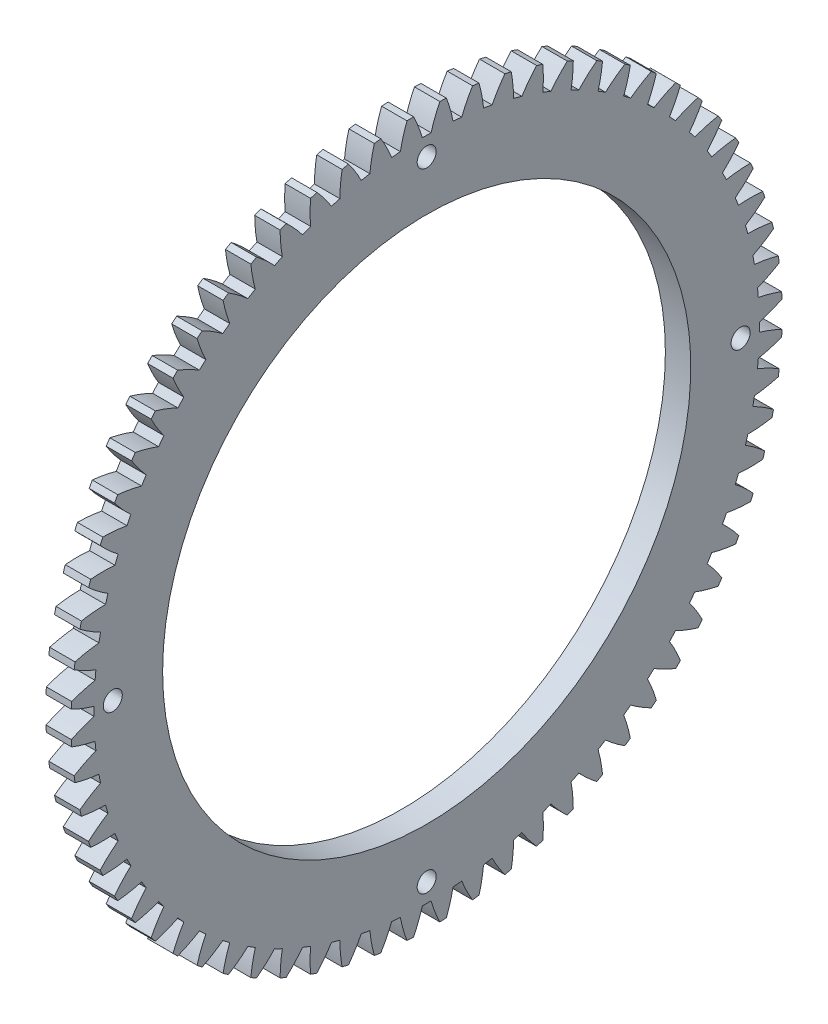
SolidWorks part; units mm, degrees
ref_plane "Plane1" through (0, 0, 0) normal (0, 0, 1) x (1, 0, 0)
ref_plane "Plane2" through (0, 0, 0) normal (0, 1, 0) x (1, 0, 0)
ref_plane "Plane3" through (0, 0, 0) normal (1, 0, 0) x (0, 0, -1)
sketch "HoldingSke" plane through (0, 0, 0) normal (0, 1, 0) x (1, 0, 0)
  line L0 (0, 0) -> (95.1501, -235.5047)
  line L1 (-15, 0) -> (100, 0) construction
  line L2 (0, 0) -> (-2.1039, 2.3779)
  line L3 (0, 0) -> (-11.863, 4.5341)
  line L4 (0, 0) -> (3.2351, 8.0072)
  line L5 (0, 0) -> (-47.5972, -17.7524)
  line L6 (0, 0) -> (-5.2639, -3.5516)
  line L7 (-2.1039, 2.3779) -> (8.8308, 51.9871)
  line L8 (-76.2, 54.61) -> (92.964, 54.61)
  line L9 (-71.009, 38.7566) -> (-53.1078, 45.2721)
  line L10 (-76.2, 71.12) -> (104.1128, 71.12)
  line L11 (0, 0) -> (-6.35, 0)
  line L12 (-76.2, 101.6) -> (-76.0984, 101.6)
  line L13 (24.9733, 27.94) -> (52.9518, 28.4284)
  line L14 (24.9733, 27.94) -> (24.9746, 27.94)
  line L15 (24.9733, 27.94) -> (100.4006, 29.5858)
  circle A0 centre (0, 0) radius 76.2
  circle A1 centre (0, 0) radius 38.1
  circle A2 centre (0, 0) radius 38.1
  circle A3 centre (0, 0) radius 76.2
  dimension "Num_teeth" = 68
  dimension "H" = 19.05
  dimension "Pitch_radius" = 180.3128
  dimension "Width" = 6.35
  dimension "Thickness" = 6.35
sketch "BasProSke" plane through (0, 0, 0) normal (0, 1, 0) x (1, 0, 0)
  line L0 (-10, 0) -> (60, 0) construction
  line L1 (0, 0) -> (0, 88.9)
  line L2 (0, 0) -> (6.35, 0)
  line L3 (6.35, 0) -> (6.35, 88.9)
  line L4 (6.35, 88.9) -> (0, 88.9)
  dimension "Thickness" = 6.35
  dimension "Diameter" = 177.8
revolve "Base-Revolve" add sketch "BasProSke" angle 360 about L0
sketch "TooCutSke" plane through (0, 0, 0) normal (1, 0, 0) x (0, 0, -1)
  line L1 (0, 0) -> (0, 107) construction
  line L2 (0, 0) -> (-2.1725, 86.3327) construction
  line L3 (0, 0) -> (-7.975, 172.4975) construction
  line L4 (-2.1725, 86.3327) -> (-3.9875, 86.2488) construction
  arc A0 (1.0901, 83.1766) -> (-1.0901, 83.1766) centre (0, 0) ccw
  arc A1 (3.2994, 88.8642) -> (-3.2994, 88.8642) centre (0, 0) ccw
  circle A2 centre (0, 0) radius 86.36 construction
  circle A3 centre (0, 0) radius 81.1519 construction
  arc A4 (-1.0901, 83.1766) -> (-3.2994, 88.8642) centre (-34.2689, 73.5613) ccw
  arc A5 (3.2994, 88.8642) -> (1.0901, 83.1766) centre (34.2689, 73.5613) ccw
extrude "ToothCut" cut sketch "TooCutSke" along normal through all
fillet "Breaks" [suppressed] radius 0.0508 tangent propagation no
fillet "RootFillets" [suppressed] radius 0.6363
pattern_circular "TeethCuts" count 68 every 5.294 about axis through (-10, 0, 0) along (1, 0, 0) of "ToothCut", "RootFillets", "Breaks"
sketch "HubNeaOneSke" plane through (0, 0, 0) normal (-1, 0, 0) x (0, 0, 1)
  circle A0 centre (0, 0) radius 38.1
  dimension "Diameter" = 76.2
extrude "HubNearOne" [suppressed] add sketch "HubNeaOneSke" along normal blind 44.4501
sketch "HubNeaBotSke" plane through (0, 0, 0) normal (-1, 0, 0) x (0, 0, 1)
  circle A0 centre (0, 0) radius 38.1
  dimension "Diameter" = 76.2
extrude "HubNearBoth" [suppressed] add sketch "HubNeaBotSke" along normal blind 22.225
ref_plane "FarPln" through (6.35, 0, 0) normal (1, 0, 0) x (0, 0, -1)
sketch "HubFarSke" plane through (6.35, 0, 0) normal (1, 0, 0) x (0, 0, -1)
  circle A0 centre (0, 0) radius 38.1
  dimension "Diameter" = 76.2
extrude "HubFar" [suppressed] add sketch "HubFarSke" along normal blind 22.225
sketch "BorSke" plane through (0, 0, 0) normal (1, 0, 0) x (0, 0, -1)
  circle A0 centre (0, 0) radius 66.04
  dimension "D1" = 132.08
extrude "Bore" cut sketch "BorSke" along normal mid plane 101.6001
sketch "KeySke" plane through (0, 0, 0) normal (1, 0, 0) x (0, 0, -1)
  line L0 (-19.05, 0) -> (-19.05, 92.964)
  line L1 (-19.05, 92.964) -> (19.05, 92.964)
  line L2 (19.05, 92.964) -> (19.05, 0)
  line L3 (0, 0) -> (0, 34) construction
  line L4 (-19.05, 0) -> (19.05, 0)
  dimension "Width" = 38.1
extrude "Keyway" [suppressed] cut sketch "KeySke" along normal mid plane 101.6001
pattern_circular "Keyway2" [suppressed] count 2 every 90 about axis through (-10, 0, 0) along (1, 0, 0) reverse direction yes
sketch "Sketch2" plane through (6.35, 0, 0) normal (1, 0, 0) x (0, 0, -1)
  line L0 (0, 78.5) -> (0, 0) construction
  line L7 (78.5, 0) -> (0, 0) construction
  circle A0 centre (0, 0) radius 85.5 construction
  circle A1 centre (0, 78.5) radius 2.3812
  circle A2 centre (78.5, 0) radius 2.3813
  circle A3 centre (0, -78.5) radius 2.3813
  circle A4 centre (-78.5, 0) radius 2.3813
  point P3 (6.9506, -0.2673)
  point P4 (0, 0)
  point P5 (0, 0)
  point P18 (0, 0)
  dimension "D1" = 171
  dimension "D4" = 4.7625
  dimension "D5" = 78.5
  dimension "D6" = 4
extrude "Cut-Extrude1" cut sketch "Sketch2" against normal through all contours A4 | A3 | A2 | A1
equation "' \"Pitch@HoldingSke\" = 4"
equation "' \"Num_teeth@HoldingSke\" = 12"
equation "' \"Ap@HoldingSke\" =  20"
equation "' \"Ap@HoldingSke\" = 20"
equation "' \"Width@HoldingSke\" = 0.5"
equation "' \"Hub_dia@HoldingSke\"= 1"
equation "' \"Hub_dia@HoldingSke\" = 1"
equation "' \"Overall_len@HoldingSke\" = 1.0"
equation "' \"Bore@HoldingSke\" = 0.75"
equation "' \"T_dim@HoldingSke\" = 0.85"
equation "' \"Width@KeySke\" = 0.25"
equation "' \"Show_teeth@HoldingSke\" = 13"
equation "' \"Backlash@HoldingSke\" = 0.009"
equation "' \"Addendum_fac@HoldingSke\" = 1.0"
equation "' \"Dedendum_fac@HoldingSke\" = 1.25"
equation "' \"Dedendum_add@HoldingSke\" = 0.00005"
equation "' \"Clearance_fac@HoldingSke\" = 0.25"
equation "' \"Pitch@HoldingSke\" = 0.5"
equation "' \"Num_teeth@HoldingSke\" = 23"
equation "' \"Show_teeth@HoldingSke\" = 23"
equation "' \"Backlash@HoldingSke\" = 0.0375"
equation "\"Overcut_dia@TooCutSke\" = (\"Num_teeth@HoldingSke\" + 2 * \"Addendum_fac@HoldingSke\") / \"Pitch@HoldingSke\" + 0.002"
equation "\"Pitch_dia@TooCutSke\" = \"Num_teeth@HoldingSke\" / \"Pitch@HoldingSke\""
equation "\"Base_dia@TooCutSke\" = \"Num_teeth@HoldingSke\" / \"Pitch@HoldingSke\" * cos((\"Ap@HoldingSke\"  * 3.14159265 / 180))"
equation "\"Root_dia@TooCutSke\" = (\"Num_teeth@HoldingSke\" + 2) / \"Pitch@HoldingSke\" - 2 * (\"Addendum_fac@HoldingSke\" + \"Dedendum_fac@HoldingSke\") / \"Pitch@HoldingSke\" - \"Dedendum_add@HoldingSke\" * 2"
equation "\"Half_ang@TooCutSke\" = 180 / \"Num_teeth@HoldingSke\""
equation "\"Half_CT@TooCutSke\" = \"Num_teeth@HoldingSke\" / \"Pitch@HoldingSke\" * sin((3.14159265 / 2 / \"Num_teeth@HoldingSke\")) / 2 - 7 * \"Backlash@HoldingSke\" / 4"
equation "\"Flank_rad@TooCutSke\" = \"Num_teeth@HoldingSke\" / \"Pitch@HoldingSke\" / 5"
equation "\"Radius@RootFillets\" = \"Clearance_fac@HoldingSke\" / \"Pitch@HoldingSke\" + \"Dedendum_add@HoldingSke\""
equation "\"Break_rad@Breaks\" = 0.02 / \"Pitch@HoldingSke\""
equation "\"Thickness@HoldingSke\" = \"Width@HoldingSke\""
equation "\"OAL@HoldingSke\" = \"Thickness@HoldingSke\""
equation "\"MHD@HoldingSke\" = (\"Num_teeth@HoldingSke\" + 2) / \"Pitch@HoldingSke\" - 2 * (\"Addendum_fac@HoldingSke\" + \"Dedendum_fac@HoldingSke\")  / \"Pitch@HoldingSke\" - \"Dedendum_add@HoldingSke\" * 2"
equation "\"MBD@HoldingSke\" = (\"Num_teeth@HoldingSke\" + 2) / \"Pitch@HoldingSke\" - 2 * (\"Addendum_fac@HoldingSke\" + \"Dedendum_fac@HoldingSke\")  / \"Pitch@HoldingSke\" - \"Dedendum_add@HoldingSke\" * 2 - 0.002"
equation "\"MHD@HoldingSke\" = ((sgn( \"MHD@HoldingSke\" - \"Hub_dia@HoldingSke\" )-1)*( \"MHD@HoldingSke\" - \"Hub_dia@HoldingSke\" ))/-2+ \"Hub_dia@HoldingSke\""
equation "\"MBD@HoldingSke\" = ((sgn( \"MBD@HoldingSke\" - \"Bore@HoldingSke\" )-1)*( \"MBD@HoldingSke\" - \"Bore@HoldingSke\" ))/-2+ \"Bore@HoldingSke\""
equation "\"OAL@HoldingSke\" = ((sgn( \"OAL@HoldingSke\" - \"Overall_len@HoldingSke\" )+1)*( \"OAL@HoldingSke\" - \"Overall_len@HoldingSke\" ))/2 + \"Overall_len@HoldingSke\" + 0.000002"
equation "\"Num_teeth@TeethCuts\" = int( \"Show_teeth@HoldingSke\" ) + 1"
equation "\"Num_teeth@TeethCuts\" = ((sgn( \"Num_teeth@TeethCuts\" - \"Num_teeth@HoldingSke\" )-1)*( \"Num_teeth@TeethCuts\" - \"Num_teeth@HoldingSke\" ))/-2+ \"Num_teeth@HoldingSke\""
equation "\"Num_teeth@TeethCuts\" = ((sgn( \"Num_teeth@TeethCuts\" - 2.0)+1)*( \"Num_teeth@TeethCuts\" - 2.0))/2 +2.0"
equation "\"Angle@TeethCuts\" = 360.0 / \"Num_teeth@HoldingSke\""
equation "\"Diameter@BasProSke\" = (\"Num_teeth@HoldingSke\" + 2 * \"Addendum_fac@HoldingSke\") / \"Pitch@HoldingSke\""
equation "\"Thickness@BasProSke\"  = \"Thickness@HoldingSke\""
equation "' \"Fillet_rad@BasProSke\" =  \"Thickness@HoldingSke\" * 0.05"
equation "' \"Fillet_rad@BasProSke\" = \"Thickness@HoldingSke\" * 0.05"
equation "\"MHD@HoldingSke\" = ((sgn( \"MHD@HoldingSke\" - \"Root_dia@TooCutSke\" )-1)*( \"MHD@HoldingSke\" - \"Root_dia@TooCutSke\" ))/-2+ \"Root_dia@TooCutSke\""
equation "\"Diameter@HubNeaOneSke\" = \"MHD@HoldingSke\""
equation "\"Length@HubNearOne\" = \"OAL@HoldingSke\" - \"Thickness@BasProSke\""
equation "\"Diameter@HubNeaBotSke\" = \"MHD@HoldingSke\""
equation "\"Length@HubNearBoth\" = ( \"OAL@HoldingSke\" - \"Thickness@BasProSke\" ) / 2.0"
equation "\"Thickness@FarPln\" = \"Thickness@BasProSke\""
equation "\"Diameter@HubFarSke\" = \"MHD@HoldingSke\""
equation "\"Length@HubFar\" = ( \"OAL@HoldingSke\" - \"Thickness@BasProSke\" ) / 2.0"
equation "\"D1@Bore\" = \"OAL@HoldingSke\" * 2.0"
equation "\"D1@Keyway\" = \"OAL@HoldingSke\" * 2.0"
equation "\"Offset@KeySke\" = \"T_dim@HoldingSke\" - \"MBD@HoldingSke\" / 2.0"
